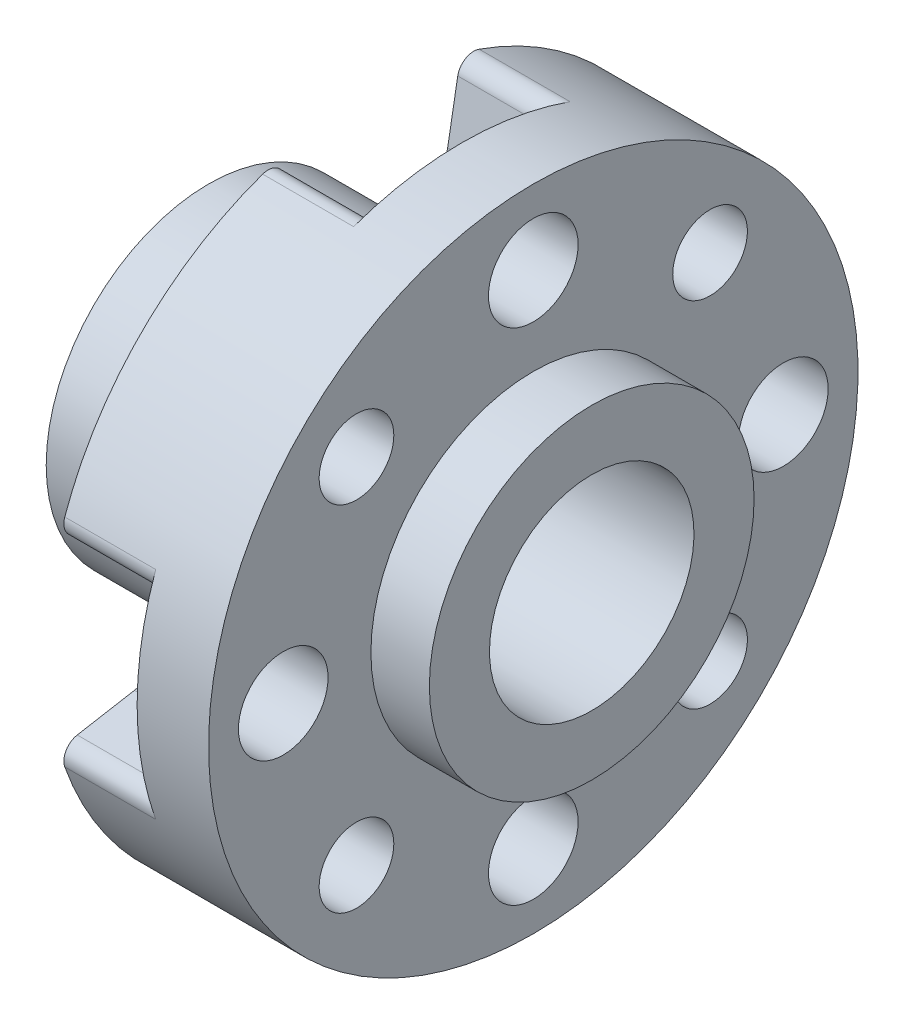
SolidWorks part; units mm, degrees
note: The reader was unsure of these and kept them because the rebuilt part matched: shared geometry of "Sketch2<3>".
other "DetailItem1"
ref_plane "Front Plane" through (0, 0, 0) normal (0, 0, 1) x (1, 0, 0)
ref_plane "Top Plane" through (0, 0, 0) normal (0, 1, 0) x (1, 0, 0)
ref_plane "Right Plane" through (0, 0, 0) normal (1, 0, 0) x (0, 0, -1)
sketch "Sketch1" plane through (0, 0, 0) normal (0, 0, 1) x (1, 0, 0)
  line L0 (0, 0) -> (-14.986, 0) construction
  line L1 (-14.986, 6.35) -> (-8.636, 6.35)
  line L2 (-8.636, 6.35) -> (-8.636, 12.7)
  line L3 (-8.636, 12.7) -> (-2.286, 12.7)
  line L5 (0, 4) -> (-14.986, 4)
  line L6 (-14.986, 4) -> (-14.986, 6.35)
  line L7 (0, 0) -> (0, 4) construction
  line L8 (-14.986, 0) -> (-14.986, 4) construction
  line L9 (0, 4) -> (0, 6.35)
  line L10 (0, 6.35) -> (-2.286, 6.35)
  line L11 (-2.286, 6.35) -> (-2.286, 12.7)
  point P6 (-1.2309, 5.3915)
  point P11 (-1.5743, 4.6665)
  dimension "D1" = 12.7
  dimension "D2" = 2.286
  dimension "D3" = 12.7
  dimension "D4" = 6.35
  dimension "D5" = 4
  dimension "D6" = 6.35
revolve "Revolve1" add sketch "Sketch1" angle 360 about L0
sketch "Sketch2" plane through (-8.636, 0, 0) normal (-1, 0, 0) x (0, 0, 1)
  line L0 (0, 0) -> (-9.779, 0) construction
  line L1 (-9.2497, -3.0017) -> (-12.2018, -3.5222)
  line L2 (-9.2497, 3.0017) -> (-12.2018, 3.5222)
  line L3 (-3.0017, 9.2497) -> (-3.5222, 12.2018)
  line L4 (3.0017, 9.2497) -> (3.5222, 12.2018)
  line L5 (9.2497, 3.0017) -> (12.2018, 3.5222)
  line L6 (9.2497, -3.0017) -> (12.2018, -3.5222)
  line L7 (3.0017, -9.2497) -> (3.5222, -12.2018)
  line L8 (-3.0017, -9.2497) -> (-3.5222, -12.2018)
  line L9 (0, 0) -> (-6.9148, 6.9148) construction
  circle A0 centre (0, 0) radius 6.35 construction
  circle A1 centre (0, 0) radius 12.7
  circle A2 centre (0, 0) radius 12.7
  circle A3 centre (0, 0) radius 6.35
  circle A4 centre (-9.779, 0) radius 1.7526
  circle A5 centre (0, 9.779) radius 1.7526
  circle A6 centre (9.779, 0) radius 1.7526
  circle A7 centre (0, -9.779) radius 1.7526
  arc A12 (-9.2497, 3.0017) -> (-9.2497, -3.0017) centre (-9.779, 0) cw
  circle A13 centre (0, 0) radius 12.7 construction
  arc A14 (3.0017, 9.2497) -> (-3.0017, 9.2497) centre (0, 9.779) cw
  arc A15 (9.2497, -3.0017) -> (9.2497, 3.0017) centre (9.779, 0) cw
  arc A16 (-3.0017, -9.2497) -> (3.0017, -9.2497) centre (0, -9.779) cw
  circle A17 centre (-6.9148, 6.9148) radius 1.4605
  circle A18 centre (6.9148, 6.9148) radius 1.4605
  circle A19 centre (6.9148, -6.9148) radius 1.4605
  circle A20 centre (-6.9148, -6.9148) radius 1.4605
  point P16 (-11.7024, -10.4743)
  point P17 (0, 0)
  point P24 (0, 0)
  point P48 (0, 0)
  point P49 (0, 0)
  dimension "D3" = 3.5052
  dimension "D5" = 3.048
  dimension "D9" = 2.921
  dimension "D2" = 9.779
  dimension "D6" = 20
  dimension "D8" = 45
  dimension "D1" = 0
  dimension "D4" = 4
  dimension "D7" = 4
  dimension "D10" = 4
extrude "Cut-Extrude2" cut sketch "Sketch2<3>" against normal through all both and the other way through all
sketch "Sketch2<3>" plane through (-8.636, 0, 0) normal (-1, 0, 0) x (0, 0, 1) same geometry as "Sketch2"
extrude "Cut-Extrude1" cut sketch "Sketch2" against normal blind 3.556
fillet "Fillet1" radius 0.635 8 edges at (-6.858, 12.2018, -3.5222) (-6.858, 12.2018, 3.5222) (-6.858, 3.5222, 12.2018) (-6.858, -3.5222, 12.2018) (-6.858, -12.2018, 3.5222) (-6.858, -12.2018, -3.5222) (-6.858, -3.5222, -12.2018) (-6.858, 3.5222, -12.2018)
